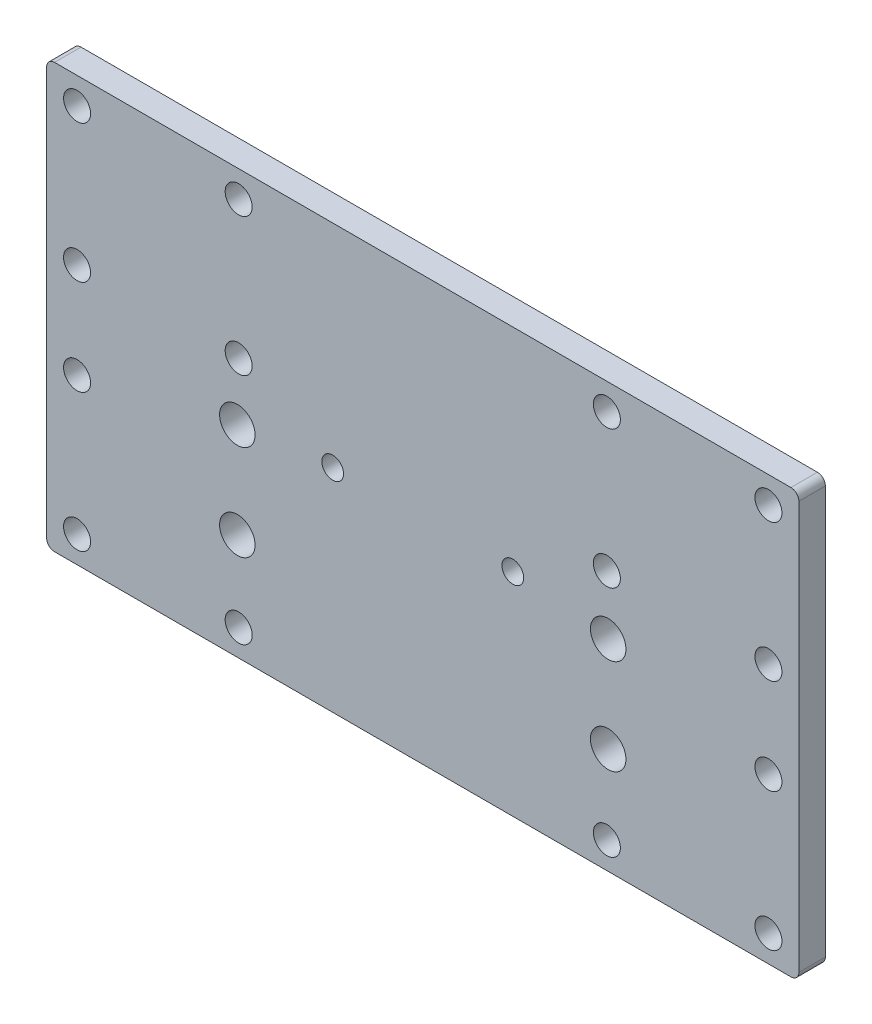
SolidWorks part; units mm, degrees
ref_plane "Front Plane" through (0, 0, 0) normal (0, 0, 1) x (1, 0, 0)
ref_plane "Top Plane" through (0, 0, 0) normal (0, 1, 0) x (1, 0, 0)
ref_plane "Right Plane" through (0, 0, 0) normal (1, 0, 0) x (0, 0, -1)
sketch "Sketch1" plane through (0, 0, 0) normal (0, 0, 1) x (1, 0, 0)
  line L1 (-71, -40) -> (71, -40)
  line L2 (-71, -40) -> (-71, 40)
  line L3 (-71, 40) -> (71, 40)
  line L4 (71, -40) -> (71, 40)
  line L5 (-71, -40) -> (71, 40) construction
  line L6 (-71, 40) -> (71, -40) construction
  point P0 (0, 0)
  dimension "D1" = 80
  dimension "D2" = 142
extrude "Boss-Extrude1" add sketch "Sketch1" along normal mid plane 5
sketch "Sketch2" plane through (0, 0, 2.5) normal (0, 0, 1) x (1, 0, 0)
  line L3 (-65.25, 40) -> (-65.25, -40)
  line L4 (-65.25, 40) -> (-65.25, -40) construction
  line L6 (65.25, -40) -> (65.25, 40)
  line L7 (65.25, -40) -> (65.25, 40) construction
  line L13 (-34.75, 40) -> (-34.75, -40)
  line L14 (-34.75, 40) -> (-34.75, -40) construction
  line L16 (34.75, -40) -> (34.75, 40)
  line L18 (34.75, -40) -> (34.75, 40) construction
  line L20 (71, 35) -> (-71, 35)
  line L21 (71, 35) -> (-71, 35) construction
  line L23 (-71, -35) -> (71, -35)
  line L24 (-71, -35) -> (71, -35) construction
  line L26 (71, 9) -> (-71, 9)
  line L27 (71, 9) -> (-71, 9) construction
  line L29 (-71, -9) -> (71, -9)
  line L30 (-71, -9) -> (71, -9) construction
  circle A0 centre (-65.25, 35) radius 2.55
  circle A1 centre (-34.75, 35) radius 2.55
  circle A2 centre (-34.75, 9) radius 2.55
  circle A3 centre (-65.25, 9) radius 2.55
  circle A4 centre (65.25, 35) radius 2.55
  circle A5 centre (65.25, 9) radius 2.55
  circle A6 centre (34.75, 9) radius 2.55
  circle A7 centre (34.75, 35) radius 2.55
  circle A8 centre (-65.25, -9) radius 2.55
  circle A10 centre (-34.75, -35) radius 2.55
  circle A11 centre (-65.25, -35) radius 2.55
  circle A13 centre (65.25, -9) radius 2.55
  circle A14 centre (65.25, -35) radius 2.55
  circle A15 centre (34.75, -35) radius 2.55
  dimension "D9" = 5.1
  dimension "D10" = 5.1
  dimension "D11" = 5.1
  dimension "D12" = 5.1
  dimension "D13" = 5.1
  dimension "D14" = 5.1
  dimension "D15" = 5.1
  dimension "D16" = 5.1
  dimension "D17" = 5.1
  dimension "D18" = 5.1
  dimension "D20" = 5.1
  dimension "D21" = 5.1
  dimension "D23" = 5.1
  dimension "D24" = 5.1
  dimension "D1" = 5.75
  dimension "D2" = 5.75
  dimension "D3" = 36.25
  dimension "D4" = 36.25
  dimension "D5" = 5
  dimension "D6" = 5
  dimension "D7" = 31
  dimension "D8" = 31
extrude "Cut-Extrude1" cut sketch "Sketch2" against normal through all
sketch "Sketch3" plane through (0, 0, 2.5) normal (0, 0, 1) x (1, 0, 0)
  line L0 (-71, -40) -> (71, -40) construction
  line L1 (-17, 0) -> (17, 0) construction
  line L7 (0, 40) -> (0, -40) construction
  line L8 (71, 40) -> (-71, 40) construction
  circle A0 centre (-17, 0) radius 2.05
  circle A3 centre (17, 0) radius 2.05
  point P0 (0, 0)
  dimension "D3" = 4.1
  dimension "D4" = 4.1
  dimension "D5" = 17
  dimension "D2" = 34
  dimension "D1" = 40
extrude "Cut-Extrude2" cut sketch "Sketch3" against normal through all
sketch "Sketch4" plane through (0, 0, 2.5) normal (0, 0, 1) x (1, 0, 0)
  line L0 (0, 40) -> (0, -40) construction
  line L1 (-35, -20) -> (35, -20) construction
  line L2 (-35, -20) -> (-35, -2) construction
  line L3 (-35, -2) -> (35, -2) construction
  line L4 (35, -20) -> (35, -2) construction
  line L5 (-35, -20) -> (35, -2) construction
  line L6 (-35, -2) -> (35, -20) construction
  line L7 (71, 40) -> (-71, 40) construction
  line L8 (-71, -40) -> (71, -40) construction
  circle A0 centre (-35, -2) radius 3.35
  circle A1 centre (35, -2) radius 3.35
  circle A2 centre (35, -20) radius 3.35
  circle A3 centre (-35, -20) radius 3.35
  point P0 (0, -11)
  dimension "D3" = 6.7
  dimension "D4" = 6.7
  dimension "D5" = 6.7
  dimension "D6" = 6.7
  dimension "D1" = 70
  dimension "D2" = 18
  dimension "D7" = 20
extrude "Cut-Extrude3" cut sketch "Sketch4" against normal through all
fillet "Fillet1" radius 1.5 4 edges at (-71, -40, 0) (71, -40, 0) (71, 40, 0) (-71, 40, 0)
equation "\"D4@Sketch3\"=\"D3@Sketch3\""
equation "\"D4@Sketch4\" = \"D3@Sketch4\""
equation "\"D5@Sketch4\"=\"D3@Sketch4\""
equation "\"D6@Sketch4\"=\"D3@Sketch4\""
equation "\"D10@Sketch2\"=\"D24@Sketch2\""
equation "\"D16@Sketch2\"=\"D24@Sketch2\""
